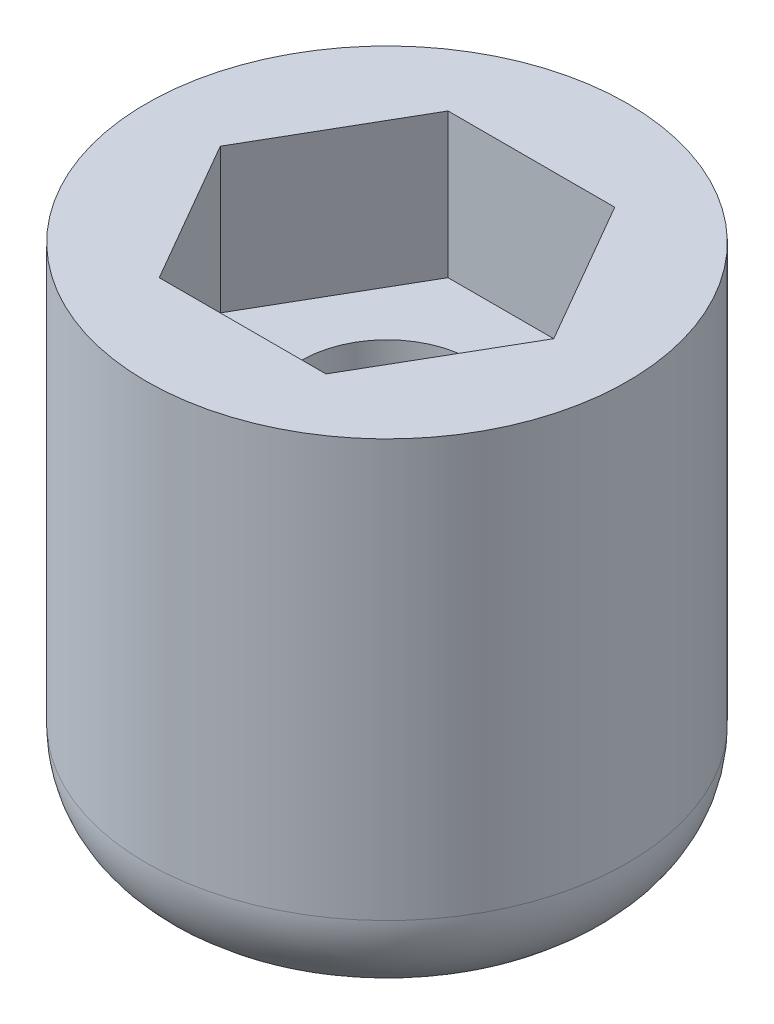
SolidWorks part; units mm, degrees
ref_plane "Front Plane" through (0, 0, 0) normal (0, 0, 1) x (1, 0, 0)
ref_plane "Top Plane" through (0, 0, 0) normal (0, 1, 0) x (1, 0, 0)
ref_plane "Right Plane" through (0, 0, 0) normal (1, 0, 0) x (0, 0, -1)
sketch "Sketch1" plane through (0, 0, 0) normal (0, 1, 0) x (1, 0, 0)
  circle A0 centre (0, 0) radius 7.5
  circle A1 centre (0, 0) radius 4.5
  dimension "D1" = 9
  dimension "D2" = 15
extrude "Boss-Extrude1" add sketch "Sketch1" along normal blind 10
sketch "Sketch2" plane through (0, 10, 0) normal (0, 1, 0) x (1, 0, 0)
  circle A0 centre (0, 0) radius 7.5
  circle A1 centre (0, 0) radius 2.65
  dimension "D1" = 5.3
  dimension "D2" = 15
extrude "Boss-Extrude2" add sketch "Sketch2" along normal blind 6
sketch "Sketch3" plane through (0, 16, 0) normal (0, 1, 0) x (1, 0, 0)
  line L1 (2.5981, 4.5) -> (-2.5981, 4.5)
  line L2 (-2.5981, 4.5) -> (-5.1962, 0)
  line L3 (-5.1962, 0) -> (-2.5981, -4.5)
  line L4 (-2.5981, -4.5) -> (2.5981, -4.5)
  line L5 (2.5981, -4.5) -> (5.1962, 0)
  line L6 (5.1962, 0) -> (2.5981, 4.5)
  circle A0 centre (0, 0) radius 4.5 construction
  dimension "D1" = 9
extrude "Cut-Extrude1" cut sketch "Sketch3" against normal blind 4.5
fillet "Fillet1" radius 3 1 edges at (0, 0, 7.5)
fillet "Fillet2" radius 1 1 edges at (0, 0, 4.5)
